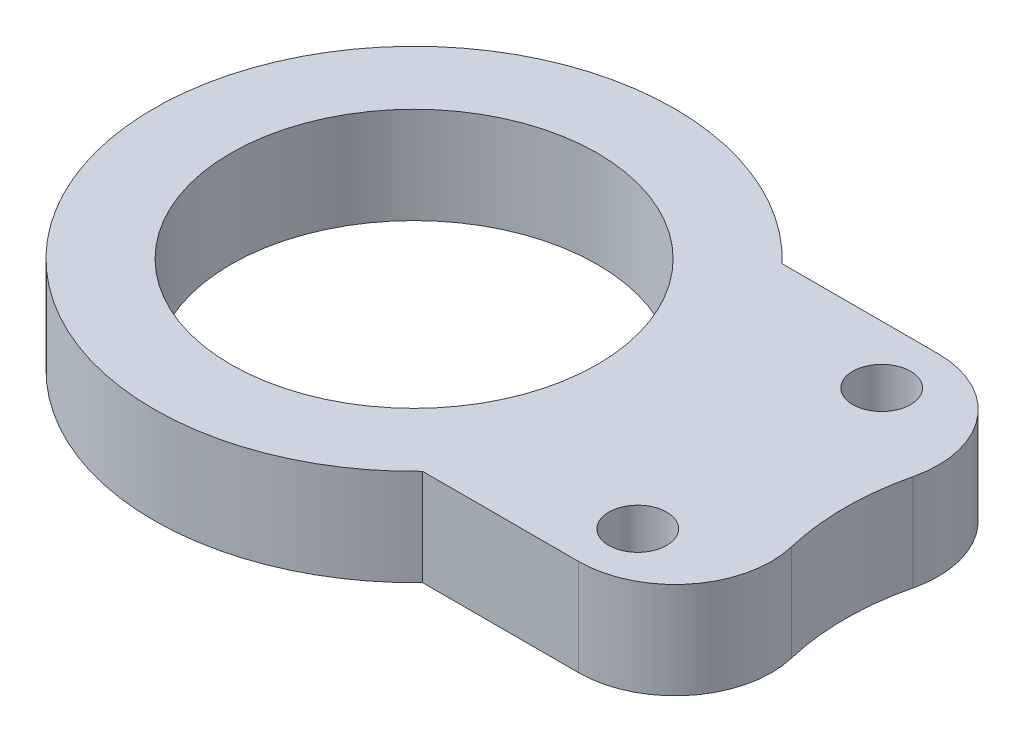
SolidWorks part; units mm, degrees
material "ABS"
ref_plane "Front Plane" through (0, 0, 0) normal (0, 0, 1) x (1, 0, 0)
ref_plane "Top Plane" through (0, 0, 0) normal (0, 1, 0) x (1, 0, 0)
ref_plane "Right Plane" through (0, 0, 0) normal (1, 0, 0) x (0, 0, -1)
sketch "Sketch1" plane through (0, 0, 0) normal (0, 1, 0) x (1, 0, 0)
  line L0 (-38, 0) -> (0, 0) construction
  line L1 (0, 0) -> (38, 0) construction
  line L2 (-38, 7.05) -> (38, 7.05)
  line L3 (-38, -7.05) -> (38, -7.05)
  circle A0 centre (-38, 0) radius 4.05
  circle A2 centre (38, 0) radius 4.05
  arc A3 (-38, 7.05) -> (-38, -7.05) centre (-38, 0) ccw
  arc A4 (38, -7.05) -> (38, 7.05) centre (38, 0) ccw
  dimension "D1" = 8.1
  dimension "D3" = 14.1
  dimension "D2" = 38
extrude "Boss-Extrude1" add sketch "Sketch1" along normal mid plane 10
scale "Scale1" scale about centroid uniform scaling yes scale factor 0.471698
sketch "Sketch2" plane through (0, 2.3585, 0) normal (0, 1, 0) x (1, 0, 0)
  line L9 (17.9245, 9.3255) -> (-17.9245, 9.3255)
  line L10 (8.1631, 9.3255) -> (-8.1631, 9.3255)
  line L12 (-17.9245, -9.3255) -> (17.9245, -9.3255)
  line L13 (-8.1631, -9.3255) -> (8.1631, -9.3255)
  arc A0 (-8.1631, 9.3255) -> (-8.1631, -9.3255) centre (-17.9245, 0) ccw
  arc A1 (8.1631, -9.3255) -> (8.1631, 9.3255) centre (17.9245, 0) ccw
  circle A2 centre (-17.9245, 0) radius 1.9104 construction
  circle A3 centre (17.9245, 0) radius 1.9104 construction
  circle A4 centre (-17.9245, 0) radius 1.9104
  circle A5 centre (17.9245, 0) radius 1.9104
  dimension "D1" = 27
  dimension "D2" = 6
  dimension "D3" = 6
extrude "Boss-Extrude3" add sketch "Sketch2" against normal through all
sketch "Sketch3" plane through (0, 2.3585, 0) normal (0, 1, 0) x (1, 0, 0)
  circle A0 centre (-17.9245, 0) radius 9.5
  circle A1 centre (17.9245, 0) radius 9.5
  dimension "D1" = 19
  dimension "D2" = 19
extrude "Cut-Extrude1" cut sketch "Sketch3" against normal through all
sketch "Sketch4" plane through (0, 2.3585, 0) normal (0, 1, 0) x (1, 0, 0)
  circle A0 centre (17.9245, 0) radius 13.5
  arc A1 (-8.1631, 9.3255) -> (-8.1631, -9.3255) centre (-17.9245, 0) ccw construction
extrude "Cut-Extrude2" cut sketch "Sketch4" against normal through all
sketch "Sketch5" plane through (0, 2.3585, 0) normal (0, 1, 0) x (1, 0, 0)
  line L6 (8.1631, 9.3255) -> (-8.1631, 9.3255) construction
  line L7 (-8.1631, -9.3255) -> (8.1631, -9.3255) construction
  circle A5 centre (0, 6.3255) radius 1.5
  circle A6 centre (0, -6.3255) radius 1.5
  dimension "D1" = 3
  dimension "D2" = 3
  dimension "D3" = 3
extrude "Cut-Extrude3" cut sketch "Sketch5" against normal through all contours A5 | A5 | A6 | A6 region at (0, 2.3585, -6.3255) region at (0, 2.3585, 6.3255)
fillet "Fillet1" radius 5 2 edges at (8.1631, 0, 9.3255) (8.1631, 0, -9.3255)
sketch "Sketch6" plane through (0, -2.3585, 0) normal (0, 1, 0) x (1, 0, 0)
  line L2 (-8.1631, -9.3255) -> (-0.0627, -9.3255)
  line L3 (-0.0627, 9.3255) -> (-8.1631, 9.3255)
  line L4 (-8.1631, -9.3255) -> (-0.0627, -9.3255)
  line L5 (-0.0627, 9.3255) -> (-8.1631, 9.3255)
  circle A0 centre (-17.9245, 0) radius 9.5 construction
  circle A1 centre (-17.9245, 0) radius 9.5
  circle A2 centre (0, -6.3255) radius 1.5 construction
  circle A3 centre (0, 6.3255) radius 1.5 construction
  arc A5 (4.7987, 3.1564) -> (4.7987, -3.1564) centre (17.9245, 0) ccw
  arc A7 (-8.1631, 9.3255) -> (-8.1631, -9.3255) centre (-17.9245, 0) ccw
  arc A11 (-8.1631, 9.3255) -> (-8.1631, -9.3255) centre (-17.9245, 0) ccw
  circle A12 centre (0, -6.3255) radius 1.5
  circle A13 centre (0, 6.3255) radius 1.5
  arc A15 (4.7987, 3.1564) -> (4.7987, -3.1564) centre (17.9245, 0) ccw
  arc A18 (-0.0627, -9.3255) -> (4.7987, -3.1564) centre (-0.0627, -4.3255) ccw
  arc A19 (-0.0627, -9.3255) -> (4.7987, -3.1564) centre (-0.0627, -4.3255) ccw
  arc A20 (4.7987, 3.1564) -> (-0.0627, 9.3255) centre (-0.0627, 4.3255) ccw
  arc A21 (4.7987, 3.1564) -> (-0.0627, 9.3255) centre (-0.0627, 4.3255) ccw
  dimension "D1" = 0
extrude "Boss-Extrude4" add sketch "Sketch6" along normal blind 5
